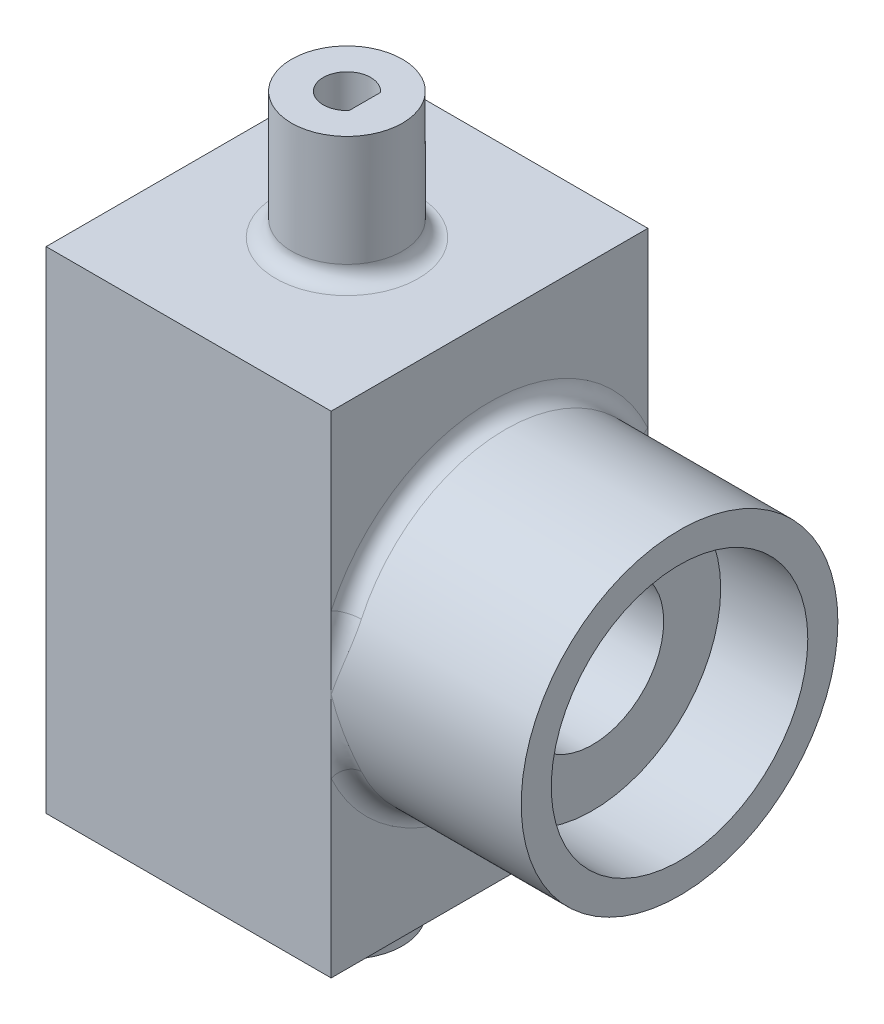
SolidWorks part; units mm, degrees
material "ABS PC"
ref_plane "Front Plane" through (0, 0, 0) normal (0, 0, 1) x (1, 0, 0)
ref_plane "Top Plane" through (0, 0, 0) normal (0, 1, 0) x (1, 0, 0)
ref_plane "Right Plane" through (0, 0, 0) normal (1, 0, 0) x (0, 0, -1)
sketch "Sketch1" plane through (0, 0, 0) normal (0, 1, 0) x (1, 0, 0)
  line L1 (-9, -10) -> (9, -10)
  line L2 (-9, -10) -> (-9, 10)
  line L3 (-9, 10) -> (9, 10)
  line L4 (9, -10) -> (9, 10)
  line L5 (-9, -10) -> (9, 10) construction
  line L6 (-9, 10) -> (9, -10) construction
  point P0 (0, 0)
  dimension "D1" = 18
  dimension "D2" = 20
extrude "Boss-Extrude1" add sketch "Sketch1" along normal blind 31
sketch "Sketch7" plane through (0, 31, 0) normal (0, 1, 0) x (1, 0, 0)
  circle A0 centre (0, 0) radius 3.5
  dimension "D1" = 7
extrude "Boss-Extrude2" add sketch "Sketch7" along normal blind 8
sketch "Sketch10" plane through (0, 0, 0) normal (0, -1, 0) x (1, 0, 0)
  circle A0 centre (0, 0) radius 3.5
  dimension "D1" = 7
extrude "Boss-Extrude3" add sketch "Sketch10" along normal blind 6
sketch "Sketch9" plane through (9, 0, 0) normal (1, 0, 0) x (0, 0, -1)
  line L2 (-10, 31) -> (10, 31) construction
  line L3 (10, 31) -> (10, 0) construction
  circle A0 centre (0, 15.5) radius 10
  point P4 (0, 31)
  point P7 (10, 15.5)
  dimension "D3" = 20
extrude "Boss-Extrude4" add sketch "Sketch9" along normal blind 12
sketch "Sketch11" plane through (0, 39, 0) normal (0, 1, 0) x (1, 0, 0)
  line L0 (1.1286, -0.9881) -> (1.1286, 0.9881)
  circle A0 centre (0, 0) radius 1.5
  dimension "D1" = 3
extrude "Cut-Extrude1" cut sketch "Sketch11" against normal blind 9 contours L0 A0
fillet "Fillet3" radius 1 4 edges at (0, 31, -3.5) (0, 0, -3.5) (9, 5.5, 0) (9, 25.5, 0)
sketch "Sketch13" plane through (-9, 0, 0) normal (-1, 0, 0) x (0, 0, 1)
  line L1 (-5.075, 21.575) -> (5.075, 21.575)
  line L2 (-5.075, 21.575) -> (-5.075, 9.425)
  line L3 (-5.075, 9.425) -> (5.075, 9.425)
  line L4 (5.075, 21.575) -> (5.075, 9.425)
  line L5 (-5.075, 21.575) -> (5.075, 9.425) construction
  line L6 (-5.075, 9.425) -> (5.075, 21.575) construction
  circle A0 centre (0, 15.5) radius 10 construction
  point P0 (0, 15.5)
  dimension "D1" = 12.15
  dimension "D2" = 10.15
extrude "Cut-Extrude2" cut sketch "Sketch13" against normal blind 15
sketch "Sketch14" plane through (21, 0, 0) normal (1, 0, 0) x (0, 0, -1)
  circle A0 centre (0, 15.5) radius 8.1
  dimension "D1" = 16.2
extrude "Cut-Extrude3" cut sketch "Sketch14" against normal blind 5.5
sketch "Sketch15" plane through (21, 0, 0) normal (1, 0, 0) x (0, 0, -1)
  circle A0 centre (0, 15.5) radius 4.5
  dimension "D1" = 9
extrude "Cut-Extrude4" cut sketch "Sketch15" against normal blind 24.5
sketch "Sketch16" plane through (0, 0, 10) normal (0, 0, 1) x (1, 0, 0)
  line L0 (-9, 31) -> (9, 31) construction
  line L1 (0, 31) -> (0, 0) construction
  line L2 (-9, 0) -> (9, 0) construction
  line L3 (0, 15.5) -> (9, 15.5) construction
  line L4 (-2.775, 3) -> (-2.775, 5)
  line L5 (2.775, 28) -> (-2.775, 28)
  line L6 (2.775, 28) -> (2.775, 26)
  line L7 (2.775, 26) -> (-2.775, 26)
  line L8 (-2.775, 28) -> (-2.775, 26)
  line L9 (2.775, 5) -> (-2.775, 5)
  line L10 (2.775, 3) -> (2.775, 5)
  line L11 (2.775, 3) -> (-2.775, 3)
  point P0 (0, 28)
  point P3 (0, 31)
  dimension "D1" = 5.55
  dimension "D2" = 2
  dimension "D3" = 3
equation "\"baseLenght\"=0.018"
equation "\"D1@Sketch1\"=\"baseLenght\""
equation "\"baseWidth\"=0.02"
equation "\"D2@Sketch1\"=\"baseWidth\""
